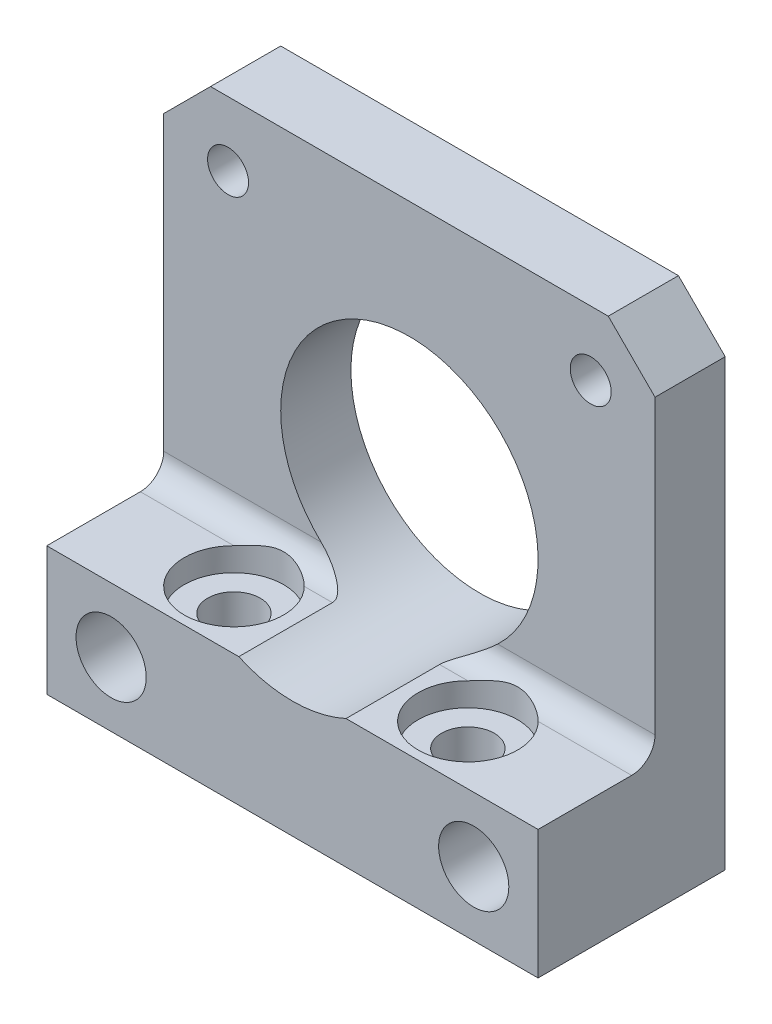
SolidWorks part; units mm, degrees
ref_plane "Plano frontal" through (0, 0, 0) normal (0, 0, 1) x (1, 0, 0)
ref_plane "Plano superior" through (0, 0, 0) normal (0, 1, 0) x (1, 0, 0)
ref_plane "Plano direito" through (0, 0, 0) normal (1, 0, 0) x (0, 0, -1)
sketch "Esboço1" plane through (0, 0, 0) normal (0, 0, 1) x (1, 0, 0)
  line L5 (21, 21) -> (-21, 21)
  line L6 (21, 21) -> (21, -21)
  line L7 (21, -21) -> (-21, -21)
  line L12 (-21, 21) -> (-21, -21)
  line L13 (21, 21) -> (-21, -21) construction
  line L14 (21, -21) -> (-21, 21) construction
  point P0 (0, 0)
  point P1 (0, 0)
  dimension "D1" = 42
  dimension "D2" = 42
extrude "Ressalto-extrusão3" add sketch "Esboço1" along normal blind 6
sketch "Esboço7" plane through (0, 0, 6) normal (0, 0, 1) x (1, 0, 0)
  line L0 (21, -21) -> (21, 21) construction
  line L1 (-21, -21) -> (21, -21)
  line L2 (-21, -21) -> (-21, -10)
  line L3 (-21, -10) -> (21, -10)
  line L4 (21, -21) -> (21, -10)
  dimension "D1" = 11
extrude "Ressalto-extrusão4" add sketch "Esboço7" along normal blind 10
sketch "Esboço6" plane through (0, 0, 0) normal (0, 0, -1) x (-1, 0, 0)
  line L0 (0, 21) -> (0, -21) construction
  line L1 (-21, 21) -> (21, 21) construction
  line L2 (21, -21) -> (-21, -21) construction
  line L4 (-15.5, 15.5) -> (15.5, 15.5) construction
  line L5 (-15.5, 15.5) -> (-15.5, -15.5) construction
  line L6 (-15.5, -15.5) -> (15.5, -15.5) construction
  line L7 (15.5, 15.5) -> (15.5, -15.5) construction
  line L8 (-15.5, 15.5) -> (15.5, -15.5) construction
  line L9 (-15.5, -15.5) -> (15.5, 15.5) construction
  circle A0 centre (0, 0) radius 11
  circle A1 centre (-15.5, 15.5) radius 1.75
  circle A2 centre (15.5, 15.5) radius 1.75
  circle A3 centre (15.5, -15.5) radius 1.75
  circle A4 centre (-15.5, -15.5) radius 1.75
  dimension "D1" = 22
  dimension "D3" = 3.5
  dimension "D2" = 31
extrude "Corte-extrusão3" cut sketch "Esboço6" against normal up to surface (16 mm away) up to face at (0, -15.5, 16)
chamfer "Chanfro1" distance 4 angle 45 2 edges at (-21, 21, 3) (21, 21, 3)
fillet "Filete1" radius 2 2 edges at (-12.7913, -10, 6) (12.7913, -10, 6)
sketch "Esboço8" plane through (0, -21, 0) normal (0, -1, 0) x (1, 0, 0)
  line L0 (0, 16) -> (0, 6) construction
  line L1 (-21, 16) -> (21, 16) construction
  line L2 (-13.75, 6) -> (-17.25, 6) construction
  line L3 (-10, 11) -> (10, 11) construction
  circle A0 centre (-10, 11) radius 2.25
  circle A1 centre (10, 11) radius 2.25
  point P11 (0, 11)
  dimension "D2" = 4.5
  dimension "D1" = 20
extrude "Corte-extrusão4" cut sketch "Esboço8" against normal up to surface (11 mm away) up to face at (-12.7913, -10, 12)
sketch "Esboço9" plane through (0, 0, 16) normal (0, 0, 1) x (1, 0, 0)
  circle A0 centre (-15.5, -15.5) radius 3
  circle A1 centre (15.5, -15.5) radius 3
  dimension "D1" = 6
extrude "Corte-extrusão5" cut sketch "Esboço9" against normal up to surface (10 mm away) up to face at (-17.25, 15.5, 6)
ref_plane "Plano1" through (0, 0, 0) normal (1, 0, 0) x (0, 0, -1)
sketch "Esboço10" plane through (0, -10, 0) normal (0, 1, 0) x (1, 0, 0)
  circle A0 centre (10, -11) radius 4.25
  circle A1 centre (-10, -11) radius 4.25
  dimension "D1" = 8.5
extrude "Corte-extrusão6" cut sketch "Esboço10" against normal offset from surface 9 and the other way up to surface up to face at (-7.75, -21, 11) other way up to face at (13.2215, -9.3255, 6.9813)
